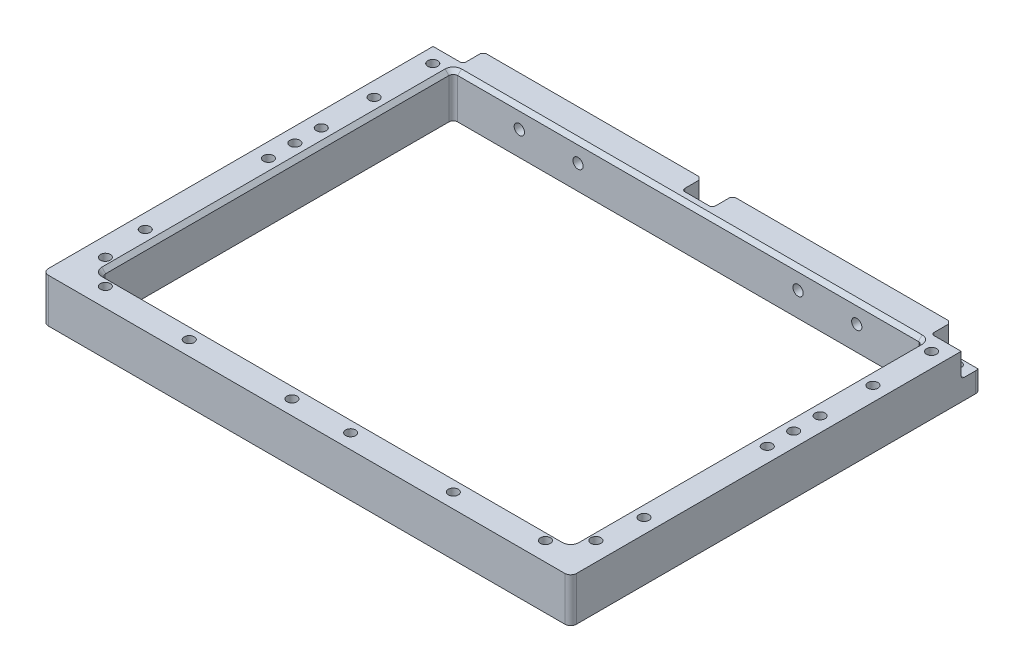
SolidWorks part; units mm, degrees
material "PLA"
ref_plane "Front Plane" through (0, 0, 0) normal (0, 0, 1) x (1, 0, 0)
ref_plane "Top Plane" through (0, 0, 0) normal (0, 1, 0) x (1, 0, 0)
ref_plane "Right Plane" through (0, 0, 0) normal (1, 0, 0) x (0, 0, -1)
sketch "Sketch1" plane through (0, 0, 0) normal (0, 1, 0) x (1, 0, 0)
  line L1 (-114.3, 88.9) -> (114.3, 88.9)
  line L2 (-114.3, 88.9) -> (-114.3, -88.9)
  line L3 (-114.3, -88.9) -> (114.3, -88.9)
  line L4 (114.3, 88.9) -> (114.3, -88.9)
  line L5 (-114.3, 88.9) -> (114.3, -88.9) construction
  line L6 (-114.3, -88.9) -> (114.3, 88.9) construction
  line L7 (-101.6, 76.2) -> (101.6, 76.2)
  line L8 (-101.6, 76.2) -> (-101.6, -76.2)
  line L9 (-101.6, -76.2) -> (101.6, -76.2)
  line L10 (101.6, 76.2) -> (101.6, -76.2)
  line L11 (-101.6, 76.2) -> (101.6, -76.2) construction
  line L12 (-101.6, -76.2) -> (101.6, 76.2) construction
  point P0 (0, 0)
  point P6 (0, 0)
  dimension "D1" = 177.8
  dimension "D2" = 152.4
  dimension "D3" = 228.6
  dimension "D4" = 203.2
extrude "Boss-Extrude1" add sketch "Sketch1" along normal blind 19.05
sketch "Sketch2" plane through (0, 0, -88.9) normal (0, 0, -1) x (-1, 0, 0)
  line L0 (114.3, 19.05) -> (114.3, 8.636)
  line L1 (114.3, 19.05) -> (114.3, 0) construction
  line L2 (114.3, 8.636) -> (101.346, 8.636)
  line L3 (101.346, 8.636) -> (101.346, 19.05)
  line L4 (-114.3, 19.05) -> (114.3, 19.05) construction
  line L5 (101.346, 19.05) -> (114.3, 19.05)
  line L6 (0, 0) -> (0, 19.05) construction
  line L7 (-6.604, 19.05) -> (6.604, 19.05)
  line L8 (6.604, 19.05) -> (6.604, 8.636)
  line L9 (6.604, 8.636) -> (-6.604, 8.636)
  line L11 (-6.604, 19.05) -> (-6.604, 8.636)
  line L12 (-101.346, 19.05) -> (-114.3, 19.05)
  line L13 (-101.346, 8.636) -> (-101.346, 19.05)
  line L14 (-114.3, 8.636) -> (-101.346, 8.636)
  line L15 (-114.3, 19.05) -> (-114.3, 8.636)
  point P16 (0, 8.636)
  dimension "D1" = 10.414
  dimension "D2" = 12.954
  dimension "D3" = 10.414
  dimension "D4" = 13.208
extrude "Cut-Extrude1" cut sketch "Sketch2" against normal blind 8.763
sketch "Sketch3" plane through (0, 8.636, 0) normal (0, 1, 0) x (1, 0, 0)
  line L0 (0, 88.9) -> (0, 80.137) construction
  line L1 (6.604, 88.9) -> (-6.604, 88.9) construction
  line L2 (-6.604, 80.137) -> (6.604, 80.137) construction
  line L3 (-107.823, 80.137) -> (-107.823, 88.9) construction
  line L4 (-114.3, 80.137) -> (-101.346, 80.137) construction
  line L5 (-101.346, 88.9) -> (-114.3, 88.9) construction
  circle A0 centre (-107.823, 84.5185) radius 2.159
  circle A1 centre (0, 84.5185) radius 2.159
  circle A2 centre (107.823, 84.5185) radius 2.159
  dimension "D1" = 4.318
  dimension "D2" = 4.318
extrude "Cut-Extrude2" cut sketch "Sketch3" against normal blind 6.35
fillet "Fillet2" radius 1.27 11 edges at (101.346, 8.636, -84.5185) (107.823, 8.636, -80.137) (-6.604, 8.636, -84.5185) (0, 8.636, -80.137) (6.604, 8.636, -84.5185) (-107.823, 8.636, -80.137) (-101.346, 8.636, -84.5185) (-101.346, 13.843, -80.137) (-6.604, 13.843, -80.137) (6.604, 13.843, -80.137) (101.346, 13.843, -80.137)
chamfer "Chamfer1" distance 1.27 angle 45 11 edges at (-108.458, 8.636, -88.9) (-101.718, 9.008, -88.9) (-101.346, 14.478, -88.9) (-6.604, 14.478, -88.9) (-6.232, 9.008, -88.9) (0, 8.636, -88.9) (6.232, 9.008, -88.9) (6.604, 14.478, -88.9) (108.458, 8.636, -88.9) (101.718, 9.008, -88.9) (101.346, 14.478, -88.9)
sketch "Sketch4" plane through (0, 0, -88.9) normal (0, 0, -1) x (-1, 0, 0)
  line L0 (0, 0) -> (0, 19.05) construction
  line L1 (-114.3, 0) -> (114.3, 0) construction
  line L2 (5.334, 19.05) -> (-5.334, 19.05) construction
  circle A0 centre (-20.32, 9.525) radius 1.905
  circle A1 centre (-81.28, 9.525) radius 1.905
  circle A2 centre (81.28, 9.525) radius 1.905
  circle A3 centre (20.32, 9.525) radius 1.905
  dimension "D1" = 3.81
  dimension "D2" = 3.81
  dimension "D3" = 20.32
  dimension "D4" = 81.28
  dimension "D5" = 9.525
  dimension "D6" = 9.525
extrude "Cut-Extrude3" cut sketch "Sketch4" against normal blind 7.112
sketch "Sketch5" plane through (0, 19.05, 0) normal (0, 1, 0) x (1, 0, 0)
  line L0 (-114.3, 80.137) -> (-114.3, -88.9) construction
  line L1 (-114.3, -88.9) -> (114.3, -88.9) construction
  line L2 (0, 0) -> (0, -50000) construction
  circle A0 centre (-95.25, -80.772) radius 2.159
  circle A1 centre (-106.172, -69.85) radius 2.159
  circle A2 centre (106.172, -69.85) radius 2.159
  circle A3 centre (95.25, -80.772) radius 2.159
  dimension "D1" = 4.318
  dimension "D2" = 4.318
  dimension "D3" = 8.128
  dimension "D4" = 8.128
  dimension "D5" = 19.05
  dimension "D6" = 19.05
extrude "Cut-Extrude4" cut sketch "Sketch5" against normal blind 7.112
fillet "Fillet3" radius 1.905 4 edges at (-101.6, 9.525, 76.2) (101.6, 9.525, 76.2) (101.6, 9.525, -76.2) (-101.6, 9.525, -76.2)
sketch "Sketch6" plane through (0, 19.05, 0) normal (0, 1, 0) x (1, 0, 0)
  line L0 (114.3, -88.9) -> (114.3, 80.137) construction
  line L1 (-99.695, -76.2) -> (99.695, -76.2) construction
  line L2 (101.6, -74.295) -> (101.6, 74.295) construction
  line L3 (0, 0) -> (0, -76.2) construction
  circle A0 centre (107.95, -50.8) radius 2.159
  circle A1 centre (107.95, 2.54) radius 2.159
  circle A2 centre (107.95, 13.97) radius 2.159
  circle A3 centre (107.95, 25.4) radius 2.159
  circle A4 centre (-107.95, 25.4) radius 2.159
  circle A5 centre (-107.95, 13.97) radius 2.159
  circle A6 centre (-107.95, 2.54) radius 2.159
  circle A7 centre (-107.95, -50.8) radius 2.159
  dimension "D1" = 4.318
  dimension "D4" = 4.318
  dimension "D5" = 4.318
  dimension "D6" = 4.318
  dimension "D2" = 6.35
  dimension "D7" = 78.74
  dimension "D8" = 90.17
  dimension "D9" = 101.6
  dimension "D10" = 6.35
  dimension "D11" = 6.35
  dimension "D12" = 6.35
extrude "Motor_Mount_Holes" cut sketch "Sketch6" against normal blind 7.112
chamfer "Chamfer2" distance 1.651 angle 45 8 edges at (-101.6, 19.05, 0) (-101.042, 19.05, 75.642) (-101.042, 19.05, -75.642) (0, 19.05, 76.2) (0, 19.05, -76.2) (101.042, 19.05, 75.642) (101.042, 19.05, -75.642) (101.6, 19.05, 0)
sketch "Sketch7" plane through (0, 19.05, 0) normal (0, 1, 0) x (1, 0, 0)
  line L0 (0, 0) -> (0, -88.9) construction
  line L1 (-114.3, -88.9) -> (114.3, -88.9) construction
  line L2 (-12.7, -76.2) -> (-12.7, -88.9) construction
  line L4 (-99.695, -76.2) -> (99.695, -76.2) construction
  circle A0 centre (-12.7, -82.55) radius 2.159
  circle A1 centre (12.7, -82.55) radius 2.159
  dimension "D1" = 4.318
  dimension "D2" = 12.7
extrude "RearBrace_MountHoles" cut sketch "Sketch7" against normal blind 7.112
sketch "Sketch8" plane through (0, 19.05, 0) normal (0, 1, 0) x (1, 0, 0)
  line L0 (114.3, 60.96) -> (101.6, 60.96) construction
  line L1 (114.3, -88.9) -> (114.3, 80.137) construction
  line L2 (101.6, -74.295) -> (101.6, 74.295) construction
  line L3 (107.95, 60.96) -> (107.95, 73.66) construction
  line L4 (-99.695, -76.2) -> (99.695, -76.2) construction
  line L5 (0, 0) -> (0, -88.9) construction
  line L6 (-114.3, -88.9) -> (114.3, -88.9) construction
  line L7 (-107.95, 60.96) -> (-107.95, 73.66) construction
  line L8 (-114.3, 60.96) -> (-101.6, 60.96) construction
  circle A0 centre (107.95, 73.66) radius 2.159
  circle A1 centre (107.95, 48.26) radius 2.159
  circle A2 centre (-107.95, 48.26) radius 2.159
  circle A3 centre (-107.95, 73.66) radius 2.159
  dimension "D1" = 4.318
  dimension "D2" = 25.4
  dimension "D3" = 137.16
extrude "SideBrace_MountHoles" cut sketch "Sketch8" against normal blind 7.112
sketch "Sketch9" plane through (0, 19.05, 0) normal (0, 1, 0) x (1, 0, 0)
  line L0 (0, -88.9) -> (0, -76.2) construction
  line L1 (-114.3, -88.9) -> (114.3, -88.9) construction
  line L2 (-99.695, -76.2) -> (99.695, -76.2) construction
  line L3 (0, -82.55) -> (-57.15, -82.55) construction
  circle A0 centre (-57.15, -82.55) radius 2.159
  circle A1 centre (57.15, -82.55) radius 2.159
  dimension "D1" = 4.318
  dimension "D2" = 114.3
extrude "BatteryMount_Holes" cut sketch "Sketch9" against normal blind 7.112
fillet "Fillet4" radius 2.54 4 edges at (-114.3, 3.683, -88.9) (114.3, 3.683, -88.9) (-114.3, 9.525, 88.9) (114.3, 9.525, 88.9)
sketch "Sketch10" plane through (0, 0, -76.2) normal (0, 0, 1) x (1, 0, 0)
  line L0 (0, 0) -> (0, 50000) construction
  line L1 (-111.76, 0) -> (111.76, 0) construction
  line L2 (101.6, 17.399) -> (101.6, 0) construction
  line L3 (47.625, 10.541) -> (73.025, 10.541) construction
  line L4 (99.695, 0) -> (-99.695, 0) construction
  line L5 (-47.625, 10.541) -> (-73.025, 10.541) construction
  circle A0 centre (47.625, 10.541) radius 2.2225
  circle A1 centre (73.025, 10.541) radius 2.2225
  circle A2 centre (-73.025, 10.541) radius 2.2225
  circle A3 centre (-47.625, 10.541) radius 2.2225
  point P4 (0, 0)
  dimension "D3" = 4.445
  dimension "D1" = 25.4
  dimension "D2" = 28.575
  dimension "D4" = 10.541
extrude "Cut-Extrude5" cut sketch "Sketch10" against normal blind 5.08
equation "\"D2@Sketch3\"=\"D1@Sketch3\""
equation "\"D2@Sketch5\"=\"D1@Sketch5\""
equation "\"D4@Sketch6\"=\"D1@Sketch6\""
equation "\"D5@Sketch6\"=\"D1@Sketch6\""
equation "\"D6@Sketch6\"=\"D1@Sketch6\""
equation "\"D10@Sketch6\"=\"D2@Sketch6\""
equation "\"D11@Sketch6\"=\"D2@Sketch6\""
equation "\"D12@Sketch6\"=\"D2@Sketch6\""
equation "\"D1@Sketch2\"=\"D3@Sketch2\""
